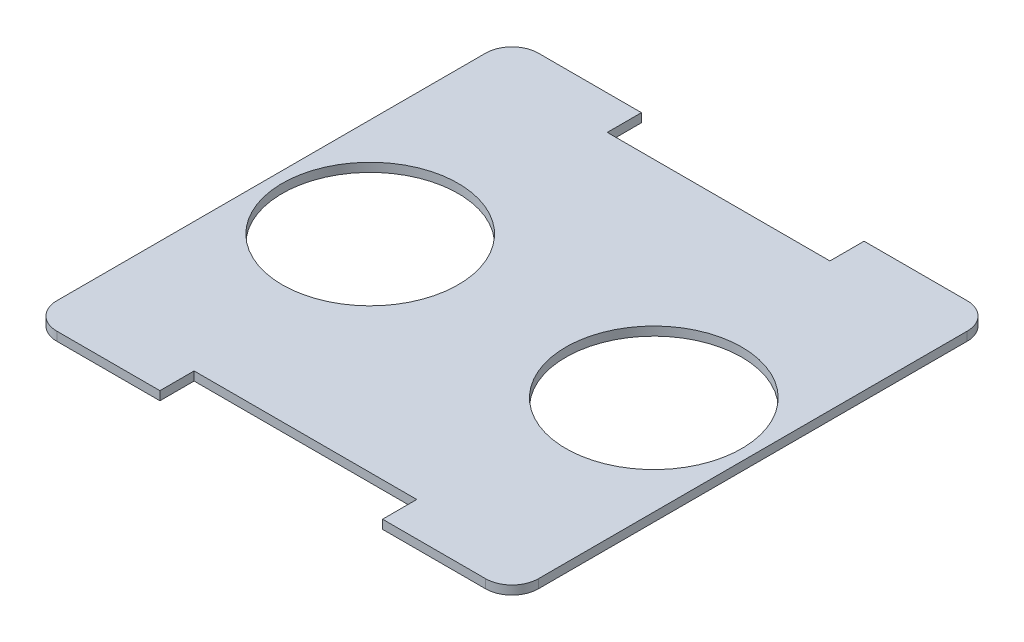
SolidWorks part; units mm, degrees
material "Aleación 1060"
ref_plane "Alzado" through (0, 0, 0) normal (0, 0, 1) x (1, 0, 0)
ref_plane "Planta" through (0, 0, 0) normal (0, 1, 0) x (1, 0, 0)
ref_plane "Vista lateral" through (0, 0, 0) normal (1, 0, 0) x (0, 0, -1)
ref_plane "Plano1" through (0, 54.7071, 0) normal (0, 1, 0) x (1, 0, 0)
sketch "Croquis1" plane through (0, 54.7071, 0) normal (0, 1, 0) x (1, 0, 0)
  line L1 (-52.102, -77.1) -> (-52.102, -452.9) construction
  line L2 (49.153, -77.1) -> (166.8935, -77.1) construction
  line L48 (-153.357, -77.1) -> (-153.357, -40) construction
  line L55 (-153.357, -77.1) -> (49.153, -77.1) construction
  line L63 (49.153, -77.1) -> (49.153, -40) construction
  line L72 (49.153, -452.9) -> (49.153, -490) construction
  line L82 (-153.357, -452.9) -> (49.153, -452.9) construction
  line L93 (-153.357, -452.9) -> (-153.357, -490) construction
  line L105 (-247.102, -46.0045) -> (-153.357, -46.0045) construction
  line L106 (49.153, -46.0045) -> (142.898, -46.0045) construction
  line L107 (166.8935, -70) -> (166.8935, -460) construction
  line L108 (142.898, -483.9955) -> (49.153, -483.9955) construction
  line L109 (-153.357, -483.9955) -> (-247.102, -483.9955) construction
  line L110 (-271.0976, -460) -> (-271.0976, -70) construction
  line L111 (-153.357, -77.1) -> (49.153, -77.1)
  line L112 (49.153, -452.9) -> (49.153, -483.9955)
  line L113 (-153.357, -452.9) -> (49.153, -452.9)
  line L114 (-153.357, -452.9) -> (-153.357, -483.9955)
  line L115 (-153.357, -77.1) -> (-153.357, -46.0045)
  line L116 (49.153, -77.1) -> (49.153, -46.0045)
  line L117 (-247.102, -46.0045) -> (-153.357, -46.0045)
  line L118 (49.153, -46.0045) -> (142.898, -46.0045)
  line L119 (166.8935, -70) -> (166.8935, -460)
  line L120 (142.898, -483.9955) -> (49.153, -483.9955)
  line L121 (-153.357, -483.9955) -> (-247.102, -483.9955)
  line L122 (-271.0976, -460) -> (-271.0976, -70)
  circle A0 centre (-181.0976, -265) radius 80
  circle A4 centre (76.8935, -265) radius 80
  arc A56 (-247.102, -46.0045) -> (-271.0976, -70) centre (-247.102, -70) ccw construction
  arc A57 (166.8935, -70) -> (142.898, -46.0045) centre (142.898, -70) ccw construction
  arc A58 (142.898, -483.9955) -> (166.8935, -460) centre (142.898, -460) ccw construction
  arc A59 (-271.0976, -460) -> (-247.102, -483.9955) centre (-247.102, -460) ccw construction
  arc A60 (-247.102, -46.0045) -> (-271.0976, -70) centre (-247.102, -70) ccw
  arc A61 (166.8935, -70) -> (142.898, -46.0045) centre (142.898, -70) ccw
  arc A62 (142.898, -483.9955) -> (166.8935, -460) centre (142.898, -460) ccw
  arc A63 (-271.0976, -460) -> (-247.102, -483.9955) centre (-247.102, -460) ccw
  point P0 (156.8935, -265)
  point P10 (-52.102, -265)
  point P11 (76.8935, -185)
  dimension "D1" = 160
  dimension "D2" = 10
extrude "Saliente-Extruir1" add sketch "Croquis1" along normal mid plane 8
sketch "Croquis2" plane through (0, 58.7071, 0) normal (0, 1, 0) x (1, 0, 0)
  line L0 (-52.102, -77.1) -> (-52.102, -452.9) construction
  line L1 (26.8935, -155) -> (126.8935, -155) construction
  line L2 (26.8935, -155) -> (26.8935, -375) construction
  line L3 (26.8935, -375) -> (126.8935, -375) construction
  line L4 (126.8935, -155) -> (126.8935, -375) construction
  line L5 (49.153, -77.1) -> (-153.357, -77.1) construction
  line L6 (-153.357, -452.9) -> (49.153, -452.9) construction
  line L7 (-231.0976, -155) -> (-231.0976, -375) construction
  line L8 (-131.0976, -375) -> (-231.0976, -375) construction
  line L9 (-131.0976, -155) -> (-131.0976, -375) construction
  line L10 (-131.0976, -155) -> (-231.0976, -155) construction
  line L11 (-271.0976, -265) -> (166.8935, -265) construction
  line L12 (-112.102, -77.1) -> (7.898, -77.1) construction
  line L13 (-112.102, -77.1) -> (-112.102, -229.5) construction
  line L14 (-112.102, -229.5) -> (7.898, -229.5) construction
  line L15 (7.898, -77.1) -> (7.898, -229.5) construction
  line L16 (-271.0976, -70) -> (-271.0976, -460) construction
  line L17 (166.8935, -460) -> (166.8935, -70) construction
  line L18 (-112.102, -300.5) -> (7.898, -300.5) construction
  line L19 (7.898, -452.9) -> (7.898, -300.5) construction
  line L20 (-112.102, -452.9) -> (7.898, -452.9) construction
  line L21 (-112.102, -452.9) -> (-112.102, -300.5) construction
  line L22 (-131.0976, -155) -> (-231.0976, -155) construction
  line L23 (-131.0976, -375) -> (-131.0976, -155) construction
  line L24 (-231.0976, -375) -> (-231.0976, -155) construction
  line L25 (-131.0976, -375) -> (-231.0976, -375) construction
  line L26 (126.8935, -375) -> (126.8935, -155) construction
  line L27 (26.8935, -155) -> (126.8935, -155) construction
  line L28 (26.8935, -375) -> (26.8935, -155) construction
  line L29 (26.8935, -375) -> (126.8935, -375) construction
  point P4 (76.8935, -265)
  point P7 (76.8935, -155)
  point P8 (26.8935, -265)
  point P18 (-181.0976, -265)
  point P23 (-52.102, -77.1)
  point P42 (76.8935, -265)
  dimension "D1" = 100
  dimension "D2" = 220
  dimension "D3" = 152.4
  dimension "D4" = 120
